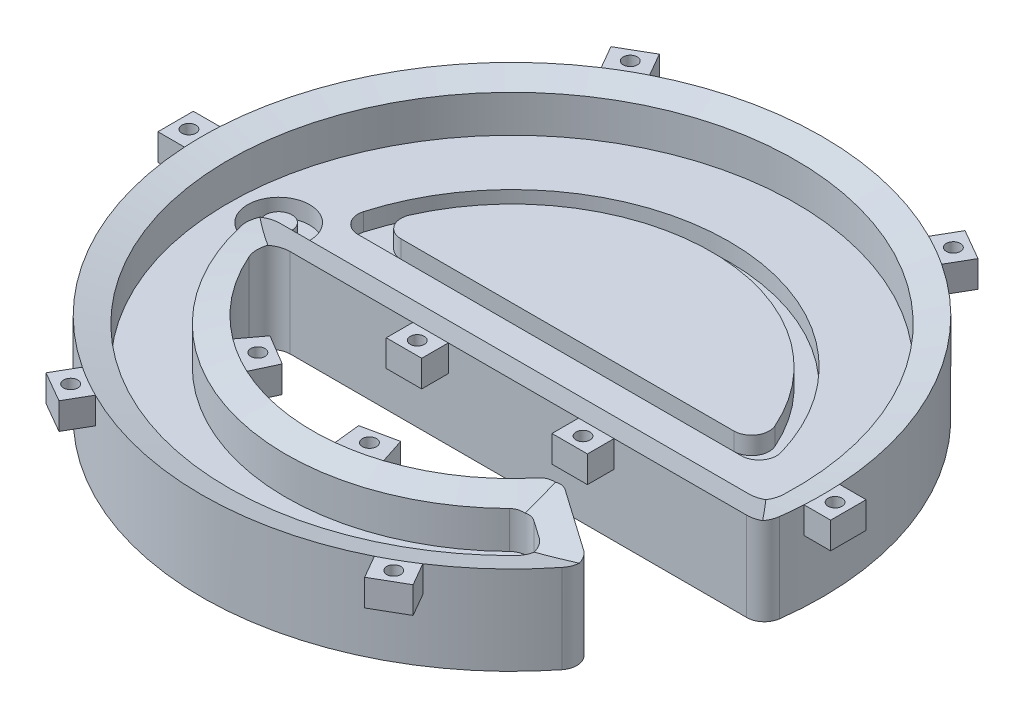
SolidWorks part; units mm, degrees
ref_plane "Front Plane" through (0, 0, 0) normal (0, 0, 1) x (1, 0, 0)
ref_plane "Top Plane" through (0, 0, 0) normal (0, 1, 0) x (1, 0, 0)
ref_plane "Right Plane" through (0, 0, 0) normal (1, 0, 0) x (0, 0, -1)
sketch "Sketch2" plane through (0, 0, 0) normal (0, 1, 0) x (1, 0, 0)
  line L0 (-21.6145, -6.25) -> (21.6145, -6.25)
  line L1 (-50, 50) -> (50, 50) construction
  line L2 (-50, 50) -> (-50, -50) construction
  line L3 (-50, -50) -> (50, -50) construction
  line L4 (50, 50) -> (50, -50) construction
  line L5 (-50, 50) -> (50, -50) construction
  line L6 (-50, -50) -> (50, 50) construction
  line L7 (-21.6145, 6.25) -> (21.6145, 6.25) construction
  line L8 (28.6703, -20.0752) -> (18.4309, -12.9055)
  line L9 (21.6145, -6.25) -> (34.4374, -6.25)
  arc A0 (34.4374, -6.25) -> (28.6703, -20.0752) centre (0, 0) ccw
  arc A1 (21.6145, 6.25) -> (-21.6145, 6.25) centre (0, 0) ccw construction
  arc A2 (-21.6145, -6.25) -> (18.4309, -12.9055) centre (0, 0) ccw
  point P0 (0, 0)
  dimension "D3" = 70
  dimension "D4" = 45
  dimension "D5" = 12.5
  dimension "D1" = 100
  dimension "D2" = 100
  dimension "D6" = 6.25
  dimension "D7" = 35
extrude "Boss-Extrude1" add sketch "Sketch2" along normal blind 5
sketch "Sketch3" plane through (0, 5, 0) normal (0, 1, 0) x (1, 0, 0)
  line L0 (-21.6145, 6.25) -> (21.6145, 6.25)
  line L2 (-24.1286, 4.25) -> (24.1286, 4.25)
  arc A0 (21.6145, 6.25) -> (-21.6145, 6.25) centre (0, 0) ccw
  arc A2 (24.1286, 4.25) -> (-24.1286, 4.25) centre (0, 0) ccw
  dimension "D2" = 45
  dimension "D1" = 6.25
  dimension "D4" = 2
extrude "Cut-Extrude1" cut sketch "Sketch3" against normal blind 2
sketch "Sketch4" plane through (0, 5, 0) normal (0, 1, 0) x (1, 0, 0)
  line L4 (-21.6145, -6.25) -> (34.4374, -6.25)
  line L5 (28.6703, -20.0752) -> (18.4309, -12.9055)
  line L8 (24.3767, -20.7311) -> (19.0226, -16.9821)
  line L9 (-25.292, -3.25) -> (31.8345, -3.25)
  arc A3 (34.4374, -6.25) -> (28.6703, -20.0752) centre (0, 0) ccw
  arc A6 (-21.6145, -6.25) -> (18.4309, -12.9055) centre (0, 0) ccw
  arc A7 (31.8345, -3.25) -> (24.3767, -20.7311) centre (0, 0) ccw
  arc A8 (-25.292, -3.25) -> (19.0226, -16.9821) centre (0, 0) ccw
  dimension "D1" = 3
extrude "Boss-Extrude3" add sketch "Sketch4" along normal blind 5
sketch "Sketch6" plane through (0, 10, 0) normal (0, 1, 0) x (1, 0, 0)
  line L0 (-63.2524, 0) -> (58.7542, 0) construction
  line L1 (-37.9428, -2) -> (-37.9428, 2)
  line L2 (-37.9428, 2) -> (-34.9428, 2)
  line L3 (-37.9428, -2) -> (-34.9428, -2)
  line L4 (-17.2394, 33.8594) -> (-15.7394, 31.2614)
  line L5 (-20.7035, 31.8594) -> (-17.2394, 33.8594)
  line L6 (-20.7035, 31.8594) -> (-19.2035, 29.2614)
  line L7 (20.7035, 31.8594) -> (19.2035, 29.2614)
  line L8 (17.2394, 33.8594) -> (20.7035, 31.8594)
  line L9 (17.2394, 33.8594) -> (15.7394, 31.2614)
  line L10 (37.9428, -2) -> (34.9428, -2)
  line L11 (37.9428, 2) -> (37.9428, -2)
  line L12 (37.9428, 2) -> (34.9428, 2)
  line L13 (17.2394, -33.8594) -> (15.7394, -31.2614)
  line L14 (20.7035, -31.8594) -> (17.2394, -33.8594)
  line L15 (20.7035, -31.8594) -> (19.2035, -29.2614)
  line L16 (-20.7035, -31.8594) -> (-19.2035, -29.2614)
  line L17 (-17.2394, -33.8594) -> (-20.7035, -31.8594)
  line L18 (-17.2394, -33.8594) -> (-15.7394, -31.2614)
  line L19 (0, 0) -> (-11.56, -19.3033) construction
  line L20 (0, 0) -> (4.6947, -22.0048) construction
  line L21 (0, 0) -> (-21.6145, -6.25) construction
  line L22 (0, 0) -> (18.4309, -12.9055) construction
  line L23 (-13.4788, -18.0159) -> (-11.6817, -15.6137)
  line L24 (-11.6817, -15.6137) -> (-8.25, -17.6688)
  line L25 (-9.5192, -20.3871) -> (-8.25, -17.6688)
  line L26 (0, 0) -> (-3.6893, -22.1955) construction
  line L27 (2.4121, -22.3703) -> (2.0905, -19.3876)
  line L28 (6.0025, -18.5532) -> (2.0905, -19.3876)
  line L29 (6.9259, -21.4075) -> (6.0025, -18.5532)
  line L30 (-21.6145, -6.25) -> (34.4374, -6.25) construction
  line L31 (-4.9345, -6.25) -> (-4.9345, -9.25)
  line L32 (-2.9345, -6.25) -> (-2.9345, -9.25) construction
  line L33 (-4.9345, -9.25) -> (-0.9345, -9.25)
  line L34 (-0.9345, -6.25) -> (-0.9345, -9.25)
  line L35 (-4.9345, -6.25) -> (-0.9345, -6.25)
  line L36 (15.7541, -6.25) -> (15.7541, -8.4076) construction
  line L37 (6.4124, -6.25) -> (6.4124, -8.0206) construction
  line L38 (17.7594, -6.25) -> (13.7594, -6.25)
  line L39 (13.7594, -6.25) -> (13.7594, -9.25)
  line L40 (17.7594, -9.25) -> (13.7594, -9.25)
  line L41 (17.7594, -6.25) -> (17.7594, -9.25)
  arc A0 (34.4374, -6.25) -> (28.6703, -20.0752) centre (0, 0) ccw construction
  arc A1 (-34.9428, 2) -> (-34.9428, -2) centre (0, 0) ccw
  circle A2 centre (-36.4428, 0) radius 0.7937
  circle A3 centre (-18.2214, 31.5604) radius 0.7937
  circle A4 centre (18.2214, 31.5604) radius 0.7938
  circle A5 centre (36.4428, 0) radius 0.7937
  circle A6 centre (18.2214, -31.5604) radius 0.7937
  circle A7 centre (-18.2214, -31.5604) radius 0.7937
  arc A8 (-15.7394, 31.2614) -> (-19.2035, 29.2614) centre (0, 0) ccw
  arc A9 (19.2035, 29.2614) -> (15.7394, 31.2614) centre (0, 0) ccw
  arc A10 (34.9428, -2) -> (34.9428, 2) centre (0, 0) ccw
  arc A11 (15.7394, -31.2614) -> (19.2035, -29.2614) centre (0, 0) ccw
  arc A12 (-19.2035, -29.2614) -> (-15.7394, -31.2614) centre (0, 0) ccw
  arc A13 (-13.4788, -18.0159) -> (-9.5192, -20.3871) centre (0, 0) ccw
  circle A14 centre (-10.7365, -17.9282) radius 0.7937
  circle A15 centre (4.3594, -20.4374) radius 0.7937
  arc A16 (2.4121, -22.3703) -> (6.9259, -21.4075) centre (0, 0) ccw
  circle A17 centre (-2.9345, -7.75) radius 0.7938
  circle A18 centre (15.7594, -7.75) radius 0.7937
  point P12 (-37.9428, 0)
  point P48 (0, 0)
  point P56 (-9.9658, -16.6413)
  dimension "D4" = 1.5875
  dimension "D10" = 18.68
  dimension "D12" = 1.5875
  dimension "D16" = 1.5875
  dimension "D1" = 3
  dimension "D2" = 2
  dimension "D3" = 1.5
  dimension "D6" = 42.957
  dimension "D7" = 42.957
  dimension "D8" = 3
  dimension "D9" = 2
  dimension "D11" = 1.5
  dimension "D13" = 21.478
  dimension "D14" = 3
  dimension "D15" = 2
  dimension "D17" = 18.6833
  dimension "D18" = 9.3417
  dimension "D5" = 6
extrude "Boss-Extrude4" add sketch "Sketch6" against normal blind 3
chamfer "Chamfer1" distance 3 angle 15 4 edges at (3.2712, 10, 3.25) (-29.4334, 10, -12.557) (21.6996, 10, 18.8566) (-7.5478, 10, 24.3574) first distance on face at (1.877, 10, 5.9521)
sketch "Sketch7" plane through (0, 5, 0) normal (0, 1, 0) x (1, 0, 0)
  circle A0 centre (-27.2576, 0.9396) radius 1.5
  circle A1 centre (-27.2576, 0.9396) radius 3.5
  point P3 (-27.0208, 0.8542)
  point P4 (0, 0)
  point P5 (-27.2576, 0.9396)
  dimension "D1" = 3
  dimension "D2" = 2
extrude "Cut-Extrude2" cut sketch "Sketch7" against normal blind 2
fillet "Fillet1" radius 2 6 edges at (-21.6145, 5, 6.25) (19.0226, 7.0981, 16.9821) (24.3767, 7.0981, 20.7311) (31.8345, 7.0981, 3.25) (24.1286, 4, -4.25) (-24.1286, 4, -4.25)
fillet "Fillet2" radius 2 6 edges at (34.4374, 5, 6.25) (18.4309, 5, 12.9055) (28.6703, 5, 20.0752) (-25.292, 7.0981, 3.25) (21.6145, 4, -6.25) (-21.6145, 4, -6.25)
